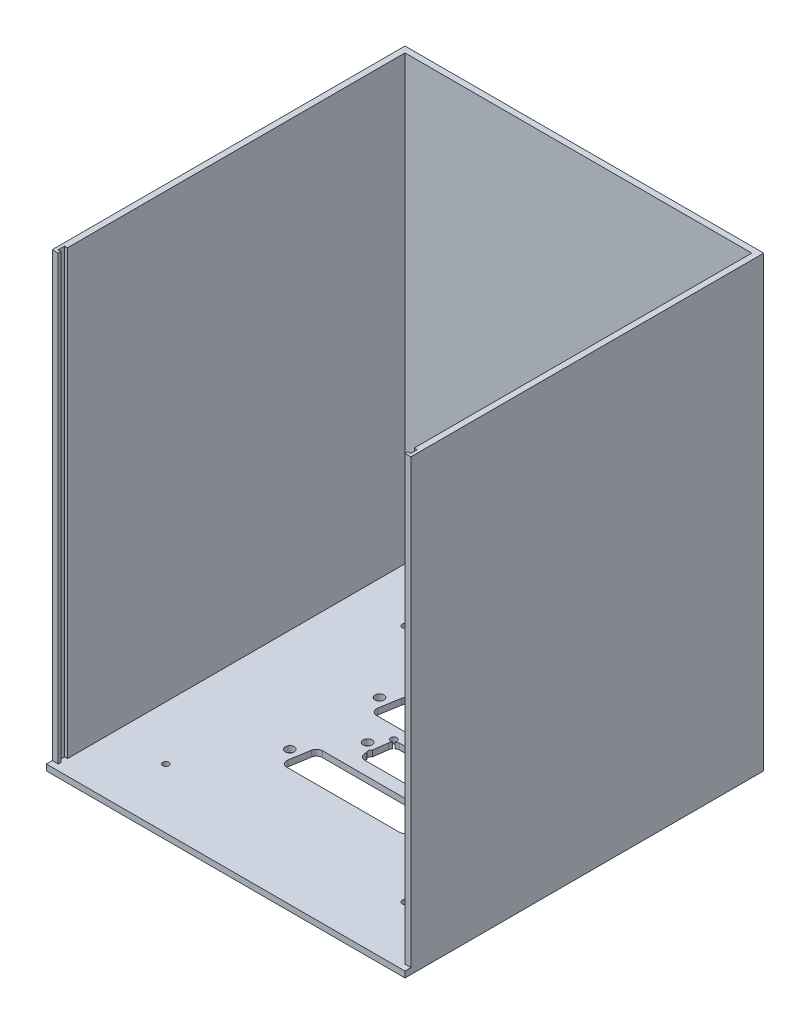
SolidWorks part; units mm, degrees
other "Markup1"
sketch "Sketch8" plane through (60, 0, -60) normal (0.7052, -0.7014, -0.1039) x (0.274, 0.4048, -0.8724)
other "Markup2"
sketch "Sketch9" plane through (60, 0, -60) normal (0.9922, -0.0018, -0.1244) x (-0.0942, 0.6423, -0.7606)
ref_plane "Front Plane" through (0, 0, 0) normal (0, 0, 1) x (1, 0, 0)
ref_plane "Top Plane" through (0, 0, 0) normal (0, 1, 0) x (1, 0, 0)
ref_plane "Right Plane" through (0, 0, 0) normal (1, 0, 0) x (0, 0, -1)
sketch "Sketch1" plane through (0, 0, 0) normal (0, 1, 0) x (1, 0, 0)
  line L5 (-60, 60) -> (60, 60)
  line L6 (-60, 60) -> (-60, -60)
  line L7 (-60, -60) -> (60, -60)
  line L8 (60, 60) -> (60, -60)
  dimension "D1" = 120
  dimension "D2" = 120
  dimension "D3" = 60
  dimension "D4" = 60
extrude "Main-Body" add sketch "Sketch1" along normal blind 150
sketch "Sketch11" plane through (0, 150, 0) normal (0, 1, 0) x (1, 0, 0)
  line L0 (-60, 60) -> (-60, -60) construction
  line L1 (58, -60) -> (-58, -60)
  line L2 (58, -60) -> (58, 58)
  line L3 (58, 58) -> (-58, 58)
  line L4 (-58, -60) -> (-58, 58)
  line L5 (58, -60) -> (-58, 58) construction
  line L6 (58, 58) -> (-58, -60) construction
  line L13 (60, 60) -> (-60, 60) construction
  point P0 (0, -1)
  dimension "D1" = 116
  dimension "D2" = 118
  dimension "D6" = 2
  dimension "D7" = 2
extrude "Hollow" cut sketch "Sketch11" against normal blind 148
sketch "Sketch12" plane through (0, 150, 0) normal (0, 1, 0) x (1, 0, 0)
  line L0 (-60, 60) -> (-60, -60) construction
  line L1 (-58, -60) -> (-60, -60)
  line L2 (-58, -60) -> (-58, -58)
  line L3 (-58, -58) -> (-60, -58)
  line L4 (-60, -60) -> (-60, -58)
  dimension "D1" = 2
extrude "Lid-Cut" cut sketch "Sketch12" against normal blind 148
mirror "Mirror-Lid-Cut" about plane through (0, 0, 0) normal (1, 0, 0) of "Lid-Cut"
sketch "Sketch13" plane through (0, 150, 0) normal (0, 1, 0) x (1, 0, 0)
  line L0 (-58, 58) -> (-58, -58) construction
  line L1 (-58, -57.1) -> (-59, -57.1)
  line L2 (-58, -57.1) -> (-58, -54.9)
  line L3 (-58, -54.9) -> (-59, -54.9)
  line L4 (-59, -57.1) -> (-59, -54.9)
  line L5 (-58, -58) -> (-60, -58) construction
  dimension "D1" = 1
  dimension "D2" = 0.9
  dimension "D3" = 2.2
extrude "Rail-Cut" cut sketch "Sketch13" against normal blind 148
sketch "Sketch2" plane through (0, 0, 0) normal (0, -1, 0) x (1, 0, 0)
  circle A0 centre (-40, 40) radius 1
  circle A1 centre (40, 40) radius 1
  circle A2 centre (40, -40) radius 1
  circle A3 centre (-40, -40) radius 1
  dimension "D1" = 40
  dimension "D3" = 2
  dimension "D2" = 40
  dimension "D4" = 2
  dimension "D5" = 2
extrude "Main-PCB-Holes" cut sketch "Sketch2" against normal up to next
sketch "Sketch3" plane through (0, 150, 0) normal (0, 1, 0) x (1, 0, 0)
  line L0 (-9, 5.23) -> (9, 5.23) construction
  circle A0 centre (-9, 5.23) radius 1.05
  circle A1 centre (9, 5.23) radius 1.05
  circle A2 centre (9, -2.27) radius 1.05
  circle A3 centre (-9, -2.27) radius 1.05
  dimension "D1" = 9
  dimension "D3" = 2.1
  dimension "D2" = 5.23
  dimension "D4" = 2
  dimension "D6" = 18
  dimension "D7" = 7.5
  dimension "D5" = 2
extrude "LED-PCB-Holes" cut sketch "Sketch3" against normal up to next
sketch "Sketch4" plane through (0, 0, 0) normal (0, -1, 0) x (1, 0, 0)
  line L0 (-12.5, 0) -> (12.5, 0) construction
  line L1 (-23.52, -15) -> (23.52, -15) construction
  line L2 (-6.8916, -5.1179) -> (6.8916, -5.1179)
  line L4 (-7.7666, 5.6321) -> (7.7666, 5.6321)
  line L6 (-17.6522, -20.0462) -> (17.6522, -20.0462)
  line L8 (-18.7772, -9.2962) -> (18.7772, -9.2962)
  line L10 (-23.52, 15) -> (23.52, 15) construction
  line L11 (-17.6522, 9.9538) -> (17.6522, 9.9538)
  line L13 (-18.7772, 20.7038) -> (18.7772, 20.7038)
  line L16 (-19.625, 11.625) -> (-20.75, 18.375)
  line L19 (20.75, 18.375) -> (19.625, 11.625)
  line L22 (-8.875, -3.375) -> (-9.75, 3.375)
  line L25 (9.75, 3.375) -> (8.875, -3.375)
  line L28 (-20.75, -11.625) -> (-19.625, -18.375)
  line L31 (19.625, -18.375) -> (20.75, -11.625)
  circle A0 centre (-12.5, 0) radius 1.5
  circle A1 centre (12.5, 0) radius 1.5
  circle A2 centre (-23.52, -15) radius 1.5
  circle A3 centre (23.52, -15) radius 1.5
  circle A4 centre (-23.52, 15) radius 1.5
  circle A5 centre (23.52, 15) radius 1.5
  arc A6 (18.7772, 20.7038) -> (20.75, 18.375) centre (18.7772, 18.7038) cw
  arc A7 (-18.7772, 20.7038) -> (-20.75, 18.375) centre (-18.7772, 18.7038) ccw
  arc A8 (17.6522, 9.9538) -> (19.625, 11.625) centre (17.6522, 11.9538) ccw
  arc A9 (-17.6522, 9.9538) -> (-19.625, 11.625) centre (-17.6522, 11.9538) cw
  arc A10 (20.75, -11.625) -> (18.7772, -9.2962) centre (18.7772, -11.2962) ccw
  arc A11 (17.6522, -20.0462) -> (19.625, -18.375) centre (17.6522, -18.0462) ccw
  arc A12 (-19.625, -18.375) -> (-17.6522, -20.0462) centre (-17.6522, -18.0462) ccw
  arc A13 (-20.75, -11.625) -> (-18.7772, -9.2962) centre (-18.7772, -11.2962) cw
  arc A14 (7.7666, 5.6321) -> (9.75, 3.375) centre (7.7666, 3.6321) cw
  arc A15 (8.875, -3.375) -> (6.8916, -5.1179) centre (6.8916, -3.1179) cw
  arc A16 (-8.875, -3.375) -> (-6.8916, -5.1179) centre (-6.8916, -3.1179) ccw
  arc A17 (-9.75, 3.375) -> (-7.7666, 5.6321) centre (-7.7666, 3.6321) cw
  point P4 (0, 0)
  point P12 (0, 5.6321)
  point P17 (0, -15)
  point P24 (0, -20.0462)
  point P29 (0, 15)
  point P32 (0, -5.1179)
  point P34 (0, 9.9538)
  point P35 (0, 20.7038)
  point P36 (0, -9.2962)
  point P38 (20.1875, -15)
  point P41 (9.3125, 0)
  point P42 (20.1875, 15)
  point P52 (21.1381, 20.7038)
  point P59 (19.3465, 9.9538)
  point P66 (21.1381, -9.2962)
  point P69 (19.3465, -20.0462)
  point P76 (10.0426, 5.6321)
  point P79 (8.6491, -5.1179)
  dimension "D1" = 3
  dimension "D2" = 3
  dimension "D8" = 3
  dimension "D7" = 3
  dimension "D14" = 3
  dimension "D15" = 3
  dimension "D4" = 41.5
  dimension "D21" = 2
  dimension "D25" = 2
  dimension "D27" = 2
  dimension "D3" = 25
  dimension "D6" = 10.75
  dimension "D9" = 47.04
  dimension "D13" = 15
  dimension "D16" = 47.04
  dimension "D18" = 10.75
  dimension "D19" = 15
  dimension "D20" = 10.75
  dimension "D28" = 39.25
  dimension "D30" = 41.5
  dimension "D31" = 39.25
  dimension "D32" = 19.5
  dimension "D33" = 17.75
extrude "Connector-Slots" cut sketch "Sketch4" against normal up to next
mirror "Mirror-Rail-Cut" about plane through (0, 0, 0) normal (1, 0, 0) of "Rail-Cut"
